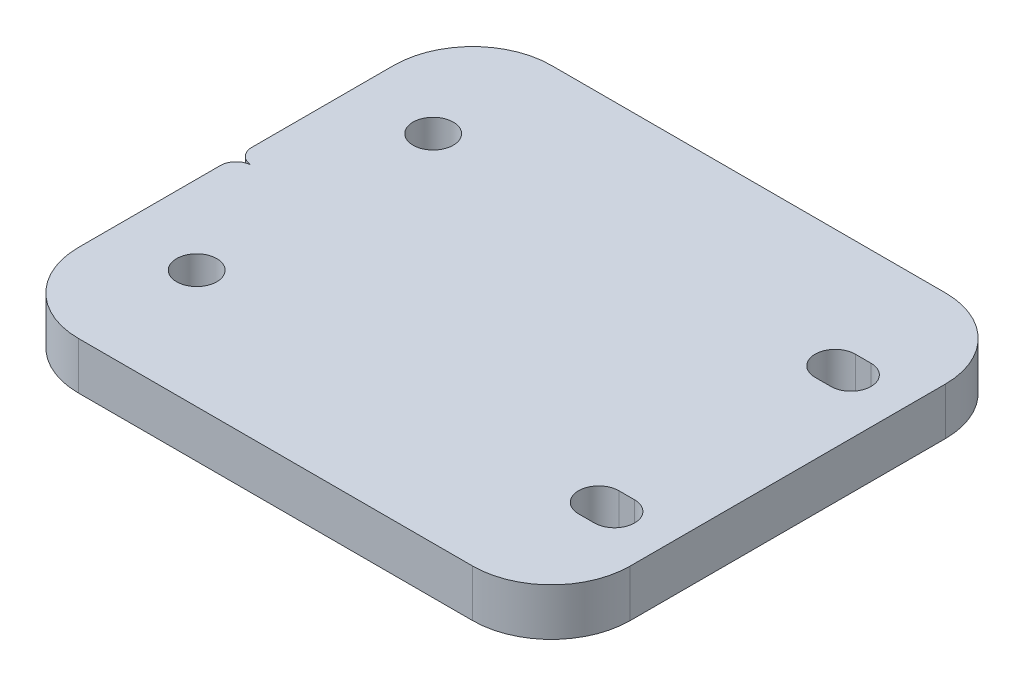
SolidWorks part; units mm, degrees
material "Клен"
ref_plane "Спереди" through (0, 0, 0) normal (0, 0, 1) x (1, 0, 0)
ref_plane "Сверху" through (0, 0, 0) normal (0, 1, 0) x (1, 0, 0)
ref_plane "Справа" through (0, 0, 0) normal (1, 0, 0) x (0, 0, -1)
sketch "Эскиз1" plane through (0, 0, 0) normal (0, 1, 0) x (1, 0, 0)
  line L0 (-41.181, -0.0464) -> (44.1026, -0.0464) construction
  line L10 (-25, -30) -> (25, -30)
  line L11 (-35, -20) -> (-35, 20)
  line L12 (-25, 30) -> (25, 30)
  line L13 (35, -20) -> (35, 20)
  line L14 (-35, -30) -> (35, 30) construction
  line L15 (-35, 30) -> (35, -30) construction
  arc A4 (25, 30) -> (35, 20) centre (25, 20) cw
  arc A5 (25, -30) -> (35, -20) centre (25, -20) ccw
  arc A6 (-25, -30) -> (-35, -20) centre (-25, -20) cw
  arc A7 (-35, 20) -> (-25, 30) centre (-25, 20) cw
  point P0 (0, 0)
  dimension "D1" = 10
  dimension "D2" = 60
  dimension "D3" = 70
extrude "Бобышка-Вытянуть1" add sketch "Эскиз1" along normal blind 6
sketch "Эскиз2" plane through (0, 0, 0) normal (0, -1, 0) x (1, 0, 0)
  line L0 (0, -37.0349) -> (0, 29.2907) construction
  line L1 (28, -15) -> (26, -15) construction
  line L2 (28, -17.55) -> (26, -17.55)
  line L3 (28, -12.45) -> (26, -12.45)
  line L6 (-46.1924, 0) -> (55.6646, 0) construction
  line L7 (28, 15) -> (26, 15) construction
  line L8 (28, 17.55) -> (26, 17.55)
  line L9 (28, 12.45) -> (26, 12.45)
  line L10 (-35, -20) -> (-35, 20) construction
  circle A0 centre (-25, -15) radius 2.55
  arc A1 (28, -17.55) -> (28, -12.45) centre (28, -15) ccw
  arc A2 (26, -12.45) -> (26, -17.55) centre (26, -15) ccw
  arc A3 (28, 17.55) -> (28, 12.45) centre (28, 15) cw
  arc A4 (26, 12.45) -> (26, 17.55) centre (26, 15) cw
  circle A5 centre (-25, 15) radius 2.55
  point P7 (27, -15)
  point P12 (27, -17.55)
  point P21 (27, 15)
  dimension "D1" = 5.1
  dimension "D2" = 5.1
  dimension "D3" = 2
  dimension "D4" = 53
  dimension "D5" = 10
  dimension "D6" = 30
extrude "Вырез-Вытянуть1" cut sketch "Эскиз2" against normal through all
sketch "Эскиз3" plane through (0, 0, 0) normal (0, -1, 0) x (1, 0, 0)
  line L0 (-33, 0) -> (27.7687, 0) construction
  line L1 (-35, -20) -> (-35, 20) construction
  line L2 (-35, -2) -> (-35, 2)
  arc A0 (-33, 0) -> (-35, -2) centre (-33, -2) ccw
  arc A1 (-33, 0) -> (-35, 2) centre (-33, 2) cw
  point P3 (-35, -2)
  point P4 (-33, 0)
  point P7 (-35, 2)
  dimension "D2" = 2
  dimension "D1" = 2
extrude "Вырез-Вытянуть2" cut sketch "Эскиз3" against normal through all
equation "\"D2@Эскиз2\"=\"D1@Эскиз2\""
